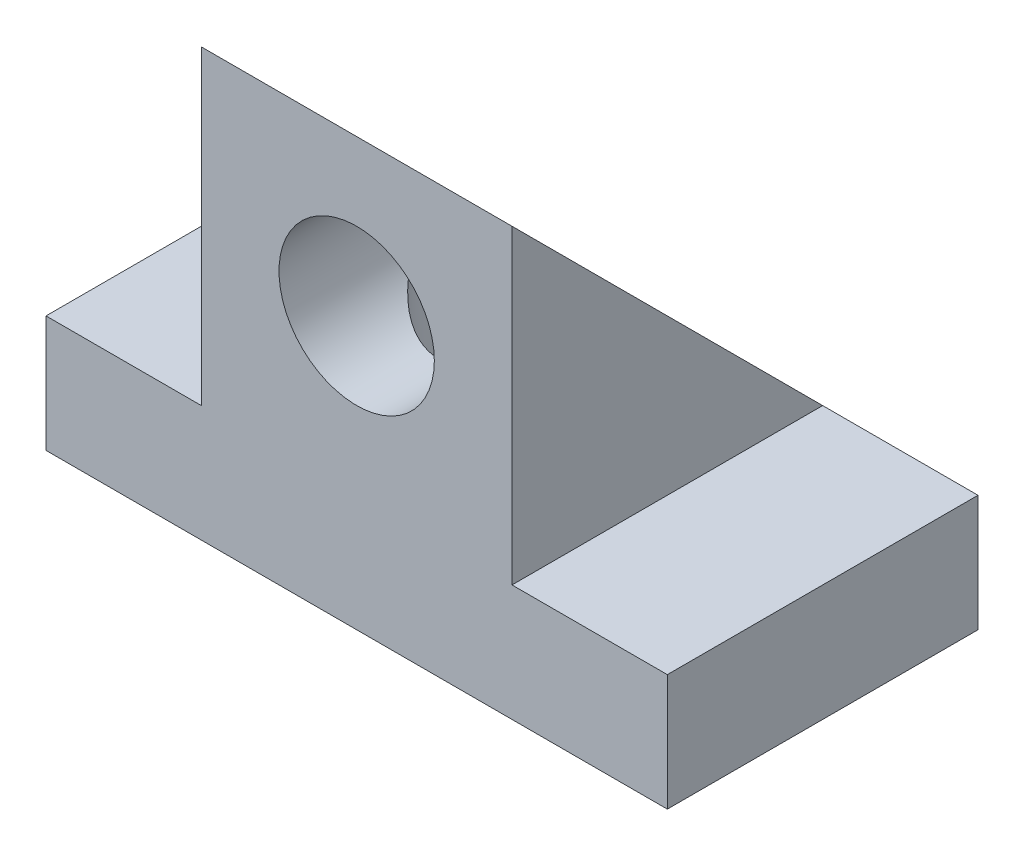
SolidWorks part; units mm, degrees
material "PET"
ref_plane "Front Plane" through (0, 0, 0) normal (1, 0, 0) x (0, 1, 0)
ref_plane "Top Plane" through (0, 0, 0) normal (0, 0, 1) x (0, 1, 0)
ref_plane "Right Plane" through (0, 0, 0) normal (0, 1, 0) x (-1, 0, 0)
sketch "Sketch1" plane through (0, 0, 0) normal (0, 1, 0) x (-1, 0, 0)
  line L1 (-10, -10) -> (10, -10)
  line L2 (-10, -10) -> (-10, 10)
  line L3 (-10, 10) -> (10, 10)
  line L4 (10, -10) -> (10, 10)
  line L5 (-10, -10) -> (10, 10) construction
  line L6 (-10, 10) -> (10, -10) construction
  circle A0 centre (0, 0) radius 6.3
  point P0 (0, 0)
  dimension "D1" = 20
  dimension "D2" = 20
extrude "Boss-Extrude1" add sketch "Sketch1" along normal blind 7.5
sketch "Sketch2" plane through (0, 7.5, 0) normal (0, 1, 0) x (-1, 0, 0)
  circle A0 centre (0, 0) radius 6.3
  circle A1 centre (0, 0) radius 4.75
extrude "Boss-Extrude2" add sketch "Sketch2" against normal blind 2
sketch "Sketch3" plane through (0, 7.5, 0) normal (0, 1, 0) x (-1, 0, 0)
  line L1 (-10, -10) -> (10, -10)
  line L2 (-10, -10) -> (-10, 10)
  line L3 (-10, 10) -> (10, 10)
  line L4 (10, -10) -> (10, 10)
  line L5 (-10, -10) -> (10, 10) construction
  line L6 (-10, 10) -> (10, -10) construction
  line L7 (-7.5, -7.5) -> (7.5, -7.5)
  line L8 (-7.5, -7.5) -> (-7.5, 7.5)
  line L9 (-7.5, 7.5) -> (7.5, 7.5)
  line L10 (7.5, -7.5) -> (7.5, 7.5)
  line L11 (-7.5, -7.5) -> (7.5, 7.5) construction
  line L12 (-7.5, 7.5) -> (7.5, -7.5) construction
  point P0 (0, 0)
  point P7 (0, 0)
  dimension "D1" = 15
extrude "Boss-Extrude3" add sketch "Sketch3" along normal blind 20
sketch "Sketch4" plane through (-10, 0, 0) normal (-1, 0, 0) x (0, -1, 0)
  line L0 (-27.5, 10) -> (0, 10) construction
  line L1 (-27.5, -10) -> (-7.5, -10)
  line L2 (-27.5, -10) -> (-27.5, 10)
  line L3 (-27.5, 10) -> (-7.5, 10)
  line L4 (-7.5, -10) -> (-7.5, 10)
  line L5 (-27.5, 10) -> (-7.5, -10)
  line M4 (-27.5, 10) -> (-27.5, -10)
  line M5 (-27.5, -10) -> (0, -10)
  dimension "D1" = 20
extrude "Cut-Extrude1" cut sketch "Sketch4" against normal blind 20 contours L5 M4 M5 region at (-10, 20.8333, -3.3333)
sketch "Sketch5" plane through (0, 8.75, -8.75) normal (0, 0.7071, -0.7071) x (-1, 0, 0)
  line L1 (-10, 26.5165) -> (10, 26.5165)
  line L2 (-10, 26.5165) -> (-10, -1.7678)
  line L3 (-10, -1.7678) -> (10, -1.7678)
  line L4 (10, 26.5165) -> (10, -1.7678)
  line L9 (-5, 4.8744) -> (5, 4.8744)
  line L10 (-5, 4.8744) -> (-5, 19.8744)
  line L11 (-5, 19.8744) -> (5, 19.8744)
  line L12 (5, 4.8744) -> (5, 19.8744)
  line L13 (-5, 4.8744) -> (5, 19.8744) construction
  line L14 (-5, 19.8744) -> (5, 4.8744) construction
  dimension "D1" = 15
  dimension "D2" = 10
extrude "Boss-Extrude6" add sketch "Sketch5" against normal blind 2
sketch "Sketch6" plane through (10, 0, 0) normal (1, 0, 0) x (0, 1, 0)
  line L0 (24.6716, 10) -> (27.5, 10)
  line M3 (27.5, 10) -> (26.0858, 11.4142)
  line M4 (26.0858, 11.4142) -> (24.6716, 10)
extrude "Cut-Extrude2" cut sketch "Sketch6" against normal blind 40 and the other way through all contours L0 M4 M3 region at (10, 26.0858, 10.4714)
sketch "Sketch7" plane through (0, 7.5, 0) normal (0, 1, 0) x (-1, 0, 0)
  line L1 (-5, -3.8891) -> (5, -3.8891)
  line L2 (-5, -3.8891) -> (-5, -5.3033)
  line L3 (-5, -5.3033) -> (5, -5.3033)
  line L4 (5, -3.8891) -> (5, -5.3033)
extrude "Cut-Extrude3" cut sketch "Sketch7" along normal blind 40
sketch "Sketch8" plane through (0, 0, 0) normal (0, -1, 0) x (1, 0, 0)
  line L0 (10, 10) -> (10, -10) construction
  line L1 (-10, 10) -> (10, 10)
  line L2 (-10, 10) -> (-10, 7)
  line L3 (-10, 7) -> (10, 7)
  line L4 (10, 10) -> (10, 7)
  line L6 (-10, 7) -> (10, 7)
  line L7 (-10, 7) -> (-10, 13)
  line L8 (-10, 13) -> (10, 13)
  line L9 (10, 7) -> (10, 13)
  line M3 (-10, 10) -> (-10, -10)
  line M5 (10, -10) -> (10, 10)
  line M6 (10, 10) -> (-10, 10)
  dimension "D1" = 3
  dimension "D2" = 6
extrude "Boss-Extrude8" add sketch "Sketch8" against normal blind 24.5 contours L3 M3 M5 M6 | L9 L8 L7 M6 region at (0, 0, 11.5) region at (0, 0, 8.5)
sketch "Sketch10" plane through (0, 0, 10) normal (0, 0, 1) x (1, 0, 0)
  line L1 (-10, 27.5) -> (10, 27.5)
  line L2 (-10, 27.5) -> (-10, 24.5)
  line L3 (-10, 24.5) -> (10, 24.5)
  line L4 (10, 27.5) -> (10, 24.5)
extrude "Cut-Extrude5" cut sketch "Sketch10" against normal blind 24.5
sketch "Sketch11" plane through (0, 24.5, 0) normal (0, 1, 0) x (-1, 0, 0)
  circle A0 centre (-6, 10) radius 2
  circle A1 centre (6, 10) radius 2
extrude "Cut-Extrude6" cut sketch "Sketch11" against normal blind 5
sketch "Sketch12" plane through (0, 0, -10) normal (0, 0, -1) x (1, 0, 0)
  line L0 (10, -7.5) -> (10, 0) construction
  line L1 (-10, -7.5) -> (10, -7.5)
  line L2 (-10, -7.5) -> (-10, -4.5)
  line L3 (-10, -4.5) -> (10, -4.5)
  line L4 (10, -7.5) -> (10, -4.5)
  dimension "D1" = 3
extrude "Boss-Extrude9" add sketch "Sketch12" along normal blind 9
sketch "Sketch13" plane through (0, 7.5, 0) normal (0, 1, 0) x (-1, 0, 0)
  circle A0 centre (-6, -14.5) radius 1.3
  circle A1 centre (6, -14.5) radius 1.3
extrude "Cut-Extrude7" cut sketch "Sketch13" against normal blind 9
sketch "Sketch14" plane through (10, 0, 0) normal (1, 0, 0) x (0, 1, 0)
  line L0 (7.5, -10) -> (27.5, 10)
  line L1 (7.5, -10) -> (27.5, -10)
  line L2 (7.5, -10) -> (7.5, 10)
  line L3 (7.5, 10) -> (27.5, 10)
  line L4 (27.5, -10) -> (27.5, 10)
  line L5 (24.5, 7) -> (24.5, 13) construction
  line L6 (0, 13) -> (24.5, 13)
  line L7 (0, 13) -> (0, 10)
  line L8 (0, 10) -> (24.5, 10)
  line L9 (24.5, 13) -> (24.5, 10)
  line M4 (24.5, 7) -> (24.5, 13)
  line M5 (24.5, 13) -> (0, 13)
  line M6 (0, 13) -> (0, -10)
  dimension "D1" = 20
  dimension "D2" = 20
extrude "Cut-Extrude8" cut sketch "Sketch14" against normal blind 27 contours L8 L3 M6 M4 M5 region at (10, 12.25, 11.5)
extrude "Boss-Extrude10" add sketch "Sketch14<3>" against normal up to surface (20 mm away) contours L3 L0 M4 region at (10, 25.5, 9) up to face at (-10, 9.125, -5.125)
sketch "Sketch14<3>" plane through (10, 0, 0) normal (1, 0, 0) x (0, 1, 0) same geometry as "Sketch14"
sketch "Sketch15" plane through (0, 24.5, 0) normal (0, -1, 0) x (1, 0, 0)
  line L0 (-8, 10) -> (8, 10)
  circle A0 centre (-6, 10) radius 2
  circle A1 centre (6, 10) radius 2
  arc M1 (-8, 10) -> (-4, 10) centre (-6, 10) ccw
  line M2 (-4, 10) -> (-8, 10)
extrude "Boss-Extrude11" add sketch "Sketch15" along normal up to surface (5 mm away) contours M2 M1 | L0 A1 region at (6, 24.5, 9.1512) region at (-6, 24.5, 9.1512) up to face at (-6, 19.5, 9)
fillet "Fillet2" radius 2 1 edges at (0, 4.5, -10)
sketch "Sketch16" plane through (0, 0, 10) normal (0, 0, 1) x (1, 0, 0)
  line L0 (10, 0) -> (10, 27.5) construction
  line L1 (-10, 27.5) -> (10, 27.5)
  line L2 (-10, 27.5) -> (-10, 7.5)
  line L3 (-10, 7.5) -> (10, 7.5)
  line L4 (10, 27.5) -> (10, 7.5)
  circle A0 centre (0, 17.5) radius 5
  dimension "D1" = 20
extrude "Cut-Extrude9" cut sketch "Sketch16" against normal blind 27 contours A0 region at (0, 17.5, 10)
sketch "Sketch17" plane through (0, 0, 7) normal (0, 0, -1) x (1, 0, 0)
  line L0 (5, -22.8033) -> (5, -12.1967) construction
  line L1 (-5, -22.8033) -> (5, -22.8033)
  line L2 (-5, -22.8033) -> (-5, -21.3891)
  line L3 (-5, -21.3891) -> (5, -21.3891)
  line L4 (5, -22.8033) -> (5, -21.3891)
  line L5 (5, -21.3891) -> (5, -22.8033) construction
extrude "Cut-Extrude10" cut sketch "Sketch17" along normal blind 27
sketch "Sketch19" plane through (-10, 0, 0) normal (-1, 0, 0) x (0, -1, 0)
  line L0 (-7.5, -10) -> (0, -10)
  line M4 (-7.5, -10) -> (-7.5, -19)
  line M5 (-7.5, -19) -> (-4.5, -19)
  line M6 (-4.5, -19) -> (-4.5, -12)
  arc M7 (-4.5, -12) -> (-2.5, -10) centre (-2.5, -12) cw
extrude "Cut-Extrude11" cut sketch "Sketch19" against normal blind 29 and the other way through all contours L0 M4 M5 M6 M7 region at (-10, 5.94, -14.3751)
sketch "Sketch20" plane through (-10, 0, 0) normal (-1, 0, 0) x (0, -1, 0)
  line L0 (-7.5, -10) -> (-7.5, 10)
  line L1 (0, 10) -> (-27.5, 10) construction
  line L6 (-27.5, 10) -> (-7.5, -10)
  line L7 (-7.5, -10) -> (0, -10)
  line L8 (0, -10) -> (0, 10)
  line L9 (0, 10) -> (-27.5, 10)
  line L11 (-7.5, -10) -> (0, -10)
  line L12 (0, -10) -> (0, 10)
  line L13 (0, 10) -> (-7.5, 10)
  dimension "D1" = 0
extrude "Boss-Extrude12" add sketch "Sketch20" along normal blind 7.5
sketch "Sketch21" plane through (10, 0, 0) normal (1, 0, 0) x (0, 1, 0)
  line L1 (7.5, -10) -> (0, -10)
  line L2 (7.5, -10) -> (7.5, 10)
  line L3 (7.5, 10) -> (0, 10)
  line L4 (0, -10) -> (0, 10)
extrude "Boss-Extrude13" add sketch "Sketch21" along normal blind 7.5
sketch "Sketch22" plane through (0, 0, 0) normal (0, -1, 0) x (1, 0, 0)
  circle A0 centre (-13.75, 6.25) radius 1.5
  circle A1 centre (13.75, 6.25) radius 1.5
  circle A2 centre (-13.75, -6.25) radius 1.5
  circle A3 centre (13.75, -6.25) radius 1.5
  dimension "D3" = 2
  dimension "D4" = 2
extrude "Cut-Extrude12" cut sketch "Sketch22" against normal blind 9.5
sketch "Sketch23" plane through (0, 0, 0) normal (0, -1, 0) x (1, 0, 0)
  circle A0 centre (-13.75, 6.25) radius 3
  circle A1 centre (13.75, 6.25) radius 3
  circle A2 centre (13.75, -6.25) radius 3
  circle A3 centre (-13.75, -6.25) radius 3
extrude "Cut-Extrude13" cut sketch "Sketch23" against normal blind 3
sketch "Sketch30" plane through (0, 0, 0) normal (0, -1, 0) x (1, 0, 0)
  circle A0 centre (0, 0) radius 7.5
extrude "Cut-Extrude14" cut sketch "Sketch30" against normal blind 2.5
thread "Thread1" pitch 1.25 method extrude trim with start face yes trim with end face yes profile "Thread Profile1" start angle 0, offset 2, length 5, pitch 1.25, diameter 15
ref_plane "Plane1" through (7.5, -2, 0) normal (0, 0, 1) x (1, 0, 0)
sketch "Thread Profile1" plane through (7.5, -2, 0) normal (0, 0, 1) x (1, 0, 0)
  line L0 (0, 0) -> (0, 1.25) construction
  line L11 (0, 0) -> (0, 1.0937)
  line L12 (0, 1.0937) -> (-0.6766, 0.7031)
  line L13 (-0.6766, 0.7031) -> (-0.6766, 0.3906)
  line L15 (-0.6766, 0.3906) -> (0, 0)
  line L17 (-0.6766, 0.5469) -> (0, 0.5469) construction
  point P2 (0, 0)
  dimension "Pitch" = 1.25
  dimension "Profile_Angle" = 60
  dimension "Profile_Land" = 0.3125
  dimension "Profile_Height" = 0.6766
sketch "Sketch31" plane through (0, 0, 10) normal (0, 0, 1) x (1, 0, 0)
  line L1 (-17.5, 0) -> (17.5, 0)
  line L2 (-17.5, 0) -> (-17.5, 35)
  line L3 (-17.5, 35) -> (17.5, 35)
  line L4 (17.5, 0) -> (17.5, 35)
  dimension "D1" = 35
  dimension "D2" = 35
extrude "Boss-Extrude15" add sketch "Sketch31" along normal blind 6
sketch "Sketch32" plane through (0, 0, 16) normal (0, 0, 1) x (1, 0, 0)
  circle A0 centre (0, 17.5) radius 10.16
extrude "Cut-Extrude16" cut sketch "Sketch32" against normal blind 6
sketch "Sketch45" plane through (0, 0, 10) normal (0, 0, 1) x (1, 0, 0)
  circle A0 centre (0, 17.5) radius 10.16
curve "Helix/Spiral1" pitch 0.7056 height 6 radius 10.16 left hand yes centre (0, 17.5, 10) axis (0, 0, 1) start towards (1, 0, 0)
sketch3d "3DSketch3"
  line L3 (10.16, 17.5, 10.7056) -> (10.16, 17.5, 10)
  line L5 (9.6731, 17.5, 10.3528) -> (9.6731, 17.5, 10.4521)
  line L6 (9.6731, 17.5, 10.4521) -> (9.6731, 17.5, 10.2535)
  line L7 (10.16, 17.5, 10.7056) -> (9.6731, 17.5, 10.4521)
  line L8 (10.16, 17.5, 10) -> (9.6731, 17.5, 10.2535)
  spline S0 degree 3 poles (10.16, 17.5, 10) (10.16, 16.1781, 10.0146) (9.6306, 13.5052, 10.0442) (7.3691, 10.1273, 10.0882) (3.9848, 7.8667, 10.1324) (-0.0066, 7.0754, 10.1765) (-3.9969, 7.8719, 10.2206) (-7.3783, 10.1356, 10.2647) (-9.6356, 13.5212, 10.3088) (-10.4247, 17.5131, 10.3529) (-9.6255, 21.503, 10.3971) (-7.3598, 24.883, 10.4412) (-3.9727, 27.1381, 10.4853) (0.0197, 27.9247, 10.5294) (4.009, 27.123, 10.5735) (7.3876, 24.8552, 10.6176) (9.6406, 21.4667, 10.6618) (10.4247, 17.4738, 10.7059) (9.6205, 13.4849, 10.75) (7.3505, 10.1078, 10.7941) (3.9606, 7.8569, 10.8382) (-0.0328, 7.0753, 10.8824) (-4.0211, 7.882, 10.9265) (-7.3968, 10.1541, 10.9706) (-9.6455, 13.5455, 11.0147) (-10.4246, 17.5393, 11.0588) (-9.6154, 21.5272, 11.1029) (-7.3412, 24.9014, 11.1471) (-3.9485, 27.148, 11.1912) (0.0459, 27.9246, 11.2353) (4.0332, 27.1129, 11.2794) (7.4061, 24.8366, 11.3235) (9.6505, 21.4424, 11.3676) (10.4246, 17.4476, 11.4118) (9.6104, 13.4607, 11.4559) (7.3319, 10.0893, 11.5) (3.9363, 7.847, 11.5441) (-0.059, 7.0754, 11.5882) (-4.0453, 7.8922, 11.6324) (-7.4153, 10.1728, 11.6765) (-9.6555, 13.5697, 11.7206) (-10.4245, 17.5655, 11.7647) (-9.6053, 21.5513, 11.8088) (-7.3226, 24.9199, 11.8529) (-3.9242, 27.1579, 11.8971) (0.0721, 27.9245, 11.9412) (4.0574, 27.1027, 11.9853) (7.4245, 24.8179, 12.0294) (9.6604, 21.4181, 12.0735) (10.4244, 17.4214, 12.1176) (9.6002, 13.4366, 12.1618) (7.3132, 10.0709, 12.2059) (3.9121, 7.8372, 12.25) (-0.0852, 7.0756, 12.2941) (-4.0694, 7.9024, 12.3382) (-7.4337, 10.1914, 12.3824) (-9.6653, 13.594, 12.4265) (-10.4243, 17.5917, 12.4706) (-9.5951, 21.5755, 12.5147) (-7.3039, 24.9383, 12.5588) (-3.8999, 27.1678, 12.6029) (0.0983, 27.9243, 12.6471) (4.0815, 27.0925, 12.6912) (7.4429, 24.7992, 12.7353) (9.6702, 21.3938, 12.7794) (10.4242, 17.3952, 12.8235) (9.5899, 13.4125, 12.8676) (7.2945, 10.0526, 12.9118) (3.8877, 7.8273, 12.9559) (-0.1114, 7.0759, 13) (-4.0936, 7.9126, 13.0441) (-7.452, 10.2101, 13.0882) (-9.6751, 13.6183, 13.1324) (-10.4241, 17.6179, 13.1765) (-9.5848, 21.5996, 13.2206) (-7.2852, 24.9566, 13.2647) (-3.8756, 27.1775, 13.3088) (0.1245, 27.924, 13.3529) (4.1056, 27.0822, 13.3971) (7.4612, 24.7805, 13.4412) (9.68, 21.3695, 13.4853) (10.4239, 17.369, 13.5294) (9.5796, 13.3884, 13.5735) (7.2758, 10.0342, 13.6176) (3.8634, 7.8176, 13.6618) (-0.1376, 7.0762, 13.7059) (-4.1177, 7.923, 13.75) (-7.4703, 10.2289, 13.7941) (-9.6848, 13.6427, 13.8382) (-10.4237, 17.6442, 13.8824) (-9.5745, 21.6237, 13.9265) (-7.2664, 24.9749, 13.9706) (-3.8512, 27.1872, 14.0147) (0.1507, 27.9236, 14.0588) (4.1297, 27.0719, 14.1029) (7.4795, 24.7617, 14.1471) (9.6897, 21.3451, 14.1912) (10.4235, 17.3427, 14.2353) (9.5693, 13.3643, 14.2794) (7.257, 10.016, 14.3235) (3.8391, 7.8079, 14.3676) (-0.1638, 7.0766, 14.4118) (-4.1417, 7.9333, 14.4559) (-7.4886, 10.2477, 14.5) (-9.6945, 13.667, 14.5441) (-10.4233, 17.6704, 14.5882) (-9.5641, 21.6477, 14.6324) (-7.2476, 24.9931, 14.6765) (-3.8269, 27.1969, 14.7206) (0.1769, 27.9232, 14.7647) (4.1537, 27.0614, 14.8088) (7.4977, 24.7429, 14.8529) (9.6993, 21.3208, 14.8971) (10.4231, 17.3165, 14.9412) (9.5588, 13.3402, 14.9853) (7.2382, 9.9977, 15.0294) (3.8147, 7.7983, 15.0735) (-0.19, 7.077, 15.1176) (-4.1658, 7.9438, 15.1618) (-7.5068, 10.2666, 15.2059) (-9.7041, 13.6914, 15.25) (-10.4229, 17.6966, 15.2941) (-9.5536, 21.6718, 15.3382) (-7.2287, 25.0113, 15.3824) (-3.8025, 27.2065, 15.4265) (0.2031, 27.9227, 15.4706) (4.1778, 27.051, 15.5147) (7.5159, 24.724, 15.5588) (9.7089, 21.2964, 15.6029) (10.4226, 17.2903, 15.6471) (9.5483, 13.3162, 15.6912) (7.2193, 9.9796, 15.7353) (3.7903, 7.7887, 15.7794) (-0.2162, 7.0776, 15.8235) (-4.1898, 7.954, 15.8676) (-7.5249, 10.2865, 15.9118) (-9.7137, 13.712, 15.9558) (-10.1859, 16.3955, 15.9854) (-10.1577, 17.7171, 16) knots 0 0 0 0 0.007353 0.014706 0.022059 0.029412 0.036765 0.044118 0.051471 0.058824 0.066176 0.073529 0.080882 0.088235 0.095588 0.102941 0.110294 0.117647 0.125 0.132353 0.139706 0.147059 0.154412 0.161765 0.169118 0.176471 0.183824 0.191176 0.198529 0.205882 0.213235 0.220588 0.227941 0.235294 0.242647 0.25 0.257353 0.264706 0.272059 0.279412 0.286765 0.294118 0.301471 0.308824 0.316176 0.323529 0.330882 0.338235 0.345588 0.352941 0.360294 0.367647 0.375 0.382353 0.389706 0.397059 0.404412 0.411765 0.419118 0.426471 0.433824 0.441176 0.448529 0.455882 0.463235 0.470588 0.477941 0.485294 0.492647 0.5 0.507353 0.514706 0.522059 0.529412 0.536765 0.544118 0.551471 0.558824 0.566176 0.573529 0.580882 0.588235 0.595588 0.602941 0.610294 0.617647 0.625 0.632353 0.639706 0.647059 0.654412 0.661765 0.669118 0.676471 0.683824 0.691176 0.698529 0.705882 0.713235 0.720588 0.727941 0.735294 0.742647 0.75 0.757353 0.764706 0.772059 0.779412 0.786765 0.794118 0.801471 0.808824 0.816176 0.823529 0.830882 0.838235 0.845588 0.852941 0.860294 0.867647 0.875 0.882353 0.889706 0.897059 0.904412 0.911765 0.919118 0.926471 0.933824 0.941176 0.948529 0.955882 0.963235 0.970588 0.977941 0.985294 0.992647 1 1 1 1 construction
  dimension "D1" = 17.5
sketch "Sketch49" plane through (0, 17.5, 0) normal (0, 1, 0) x (1, 0, 0)
  line L5 (10.16, -10.1) -> (10.16, -10.6056)
  line L9 (9.8652, -10.3528) -> (9.8652, -10.4521)
  line L10 (9.8652, -10.3528) -> (9.8652, -10.2535)
  line L11 (9.8652, -10.2535) -> (10.16, -10.1)
  line L12 (10.16, -10.6056) -> (9.8652, -10.4521)
sweep "Sweep3" add profiles "Sketch49" path "Helix/Spiral1"
sketch "Sketch52" plane through (0, 0, -10) normal (0, 0, -1) x (1, 0, 0)
  line L0 (-10, -7.5) -> (-13.75, -7.5)
  line L1 (-10, -7.5) -> (10, -7.5)
  line L2 (-10, -7.5) -> (-10, -27.5)
  line L3 (-10, -27.5) -> (10, -27.5)
  line L4 (10, -7.5) -> (10, -27.5)
  line L5 (-17.5, -7.5) -> (-10, -7.5) construction
  line L6 (-13.75, -7.5) -> (-13.75, -31.4674)
  line L7 (-13.75, -31.4674) -> (15.3699, -31.4674)
  line L8 (15.3699, -31.4674) -> (15.3699, -7.5)
  line L9 (17.5, -7.5) -> (10, -7.5) construction
  line L10 (15.3699, -7.5) -> (10, -7.5)
  line M3 (-17.5, -7.5) -> (-10, -7.5)
  line M5 (10, -7.5) -> (17.5, -7.5)
extrude "Cut-Extrude18" cut sketch "Sketch52" against normal up to surface (20 mm away) contours L7 L8 L4 L3 L2 L6 M5 M3 region at (-10.3771, 17.5, -10) up to face at (0, 20.0114, 10)
sketch "Sketch53" plane through (0, 0, 0) normal (0, -1, 0) x (1, 0, 0)
  circle A0 centre (-13.75, 6.25) radius 3
  circle A1 centre (13.75, 6.25) radius 3
  circle A2 centre (13.75, -6.25) radius 3
  circle A3 centre (-13.75, -6.25) radius 3
extrude "Boss-Extrude16" add sketch "Sketch53" against normal up to surface (7.5 mm away) up to face at (-13.75, 7.5, 4.75)
sketch "Sketch55" plane through (17.5, 0, 0) normal (1, 0, 0) x (0, 1, 0)
  line L0 (35, 10) -> (0, 10)
  line L1 (0, 16) -> (0, -10) construction
  line M2 (7.5, 10) -> (35, 10)
  line M3 (35, 10) -> (35, 16)
  line M4 (35, 16) -> (0, 16)
  line M5 (0, 16) -> (0, -10)
extrude "Cut-Extrude19" cut sketch "Sketch55" against normal blind 52 and the other way through all contours L0 M2 M3 M4 M5 region at (17.5, 17.5, 13)
sketch "Sketch56" plane through (-10, 0, 0) normal (-1, 0, 0) x (0, -1, 0)
  line L0 (-27.5, 10) -> (-7.5, 10)
  line L1 (-7.5, 10) -> (-7.5, -10)
  line L2 (-7.5, -10) -> (-27.5, 10)
  line L4 (-7.5, 10) -> (0, 10)
  line L5 (-7.5, 10) -> (-7.5, -10)
  line L6 (-7.5, -10) -> (0, -10)
  line L7 (0, 10) -> (0, -10)
  line M1 (-7.5, 10) -> (-27.5, 10)
  line M2 (-27.5, 10) -> (-7.5, -10)
  line M3 (-7.5, -10) -> (-7.5, 10)
extrude "Cut-Extrude20" cut sketch "Sketch56" against normal blind 52 flip side to cut contours M3 M1 M2 | L7 L4 L6 M3 region at (-10, 14.1667, 3.3333) region at (-10, 3.75, 0)
sketch "Sketch57" plane through (0, 7.5, 0) normal (0, 1, 0) x (-1, 0, 0)
  circle A0 centre (0, 0) radius 4.75
  circle M1 centre (0, 0) radius 4.75
  line M2 (7.5, -7.1716) -> (7.5, 7)
  line M3 (7.5, 7) -> (-7.5, 7)
  line M4 (-7.5, 7) -> (-7.5, -7.1716)
  line M5 (-7.5, -7.1716) -> (7.5, -7.1716)
extrude "Boss-Extrude18" add sketch "Sketch57" along normal up to surface (14.75 mm away) contours M5 M2 M3 M4 M1 region at (0, 7.5, -6.9652) up to face at (0, 17.5, 0)
sketch "Sketch58" plane through (0, 0, 7) normal (0, 0, 1) x (1, 0, 0)
  circle A1 centre (0, 17.5) radius 5
extrude "Cut-Extrude21" cut sketch "Sketch58" against normal blind 52
sketch "Sketch59" plane through (0, 0, 0) normal (0, -1, 0) x (1, 0, 0)
  line L1 (-17.5, -10) -> (17.5, -10)
  line L2 (-17.5, -10) -> (-17.5, 10)
  line L3 (-17.5, 10) -> (17.5, 10)
  line L4 (17.5, -10) -> (17.5, 10)
  line L5 (-17.5, -10) -> (17.5, 10) construction
  line L6 (-17.5, 10) -> (17.5, -10) construction
  line L7 (-20, -10) -> (20, -10)
  line L8 (-20, -10) -> (-20, 10)
  line L9 (-20, 10) -> (20, 10)
  line L10 (20, -10) -> (20, 10)
  line L11 (-20, -10) -> (20, 10) construction
  line L12 (-20, 10) -> (20, -10) construction
  point P0 (0, 0)
  point P7 (0, 0)
  line M2 (-17.5, 10) -> (-17.5, -10)
  line M4 (17.5, -10) -> (17.5, 10)
  dimension "D1" = 40
extrude "Boss-Extrude19" add sketch "Sketch59" against normal up to surface (7.5 mm away) contours L7 L10 L9 M4 | L9 L8 L7 M2 region at (-18.75, 0, 0) region at (18.75, 0, 0) up to face at (13.75, 7.5, 0)
